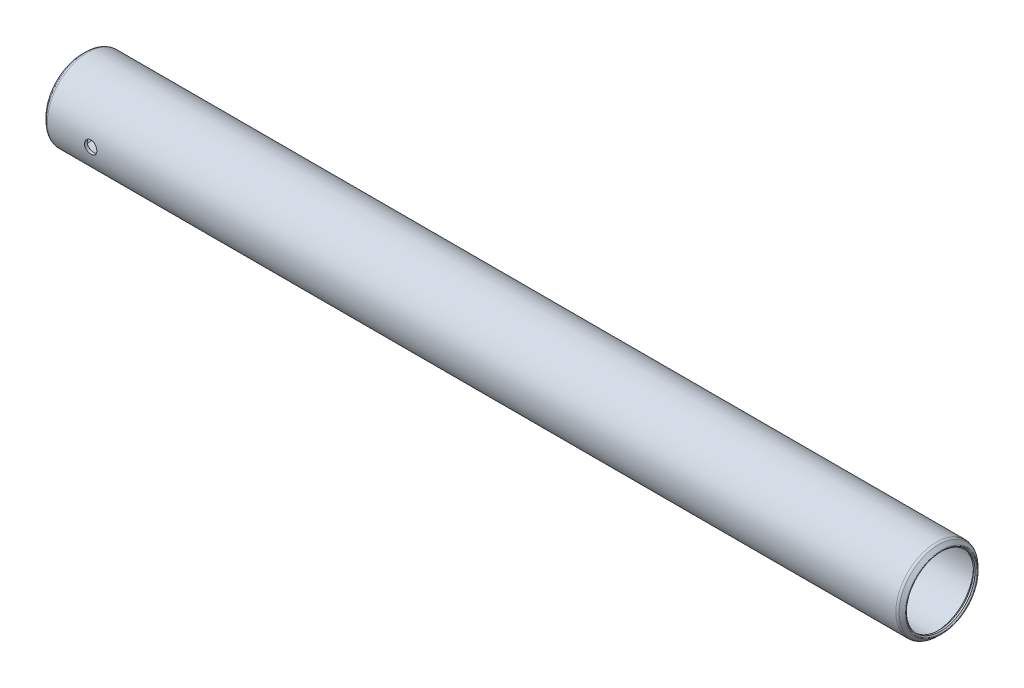
SolidWorks part; units mm, degrees
material "Cast Alloy Steel"
ref_plane "Front Plane" through (0, 0, 0) normal (0, 0, 1) x (1, 0, 0)
ref_plane "Top Plane" through (0, 0, 0) normal (0, 1, 0) x (1, 0, 0)
ref_plane "Right Plane" through (0, 0, 0) normal (1, 0, 0) x (0, 0, -1)
ref_plane "Plane1" through (164.8714, 0, 0) normal (1, 0, 0) x (0, 0, -1)
sketch "Sketch1" plane through (0, 0, 0) normal (0, 0, 1) x (1, 0, 0)
  line L0 (-0.518, 6.8362) -> (-0.3175, 6.6357)
  line L1 (-0.3175, 6.6357) -> (0, 6.6357)
  line L2 (0, 6.6357) -> (0.635, 7.2707)
  line L3 (0.635, 7.2707) -> (164.2364, 7.2707)
  line L4 (164.2364, 7.2707) -> (164.8714, 6.6357)
  line L5 (164.8714, 6.6357) -> (165.1889, 6.6357)
  line L6 (165.1889, 6.6357) -> (165.3894, 6.8362)
  line L7 (165.3894, 7.0158) -> (164.7807, 7.6245)
  line L8 (164.3316, 7.8105) -> (0.5398, 7.8105)
  line L9 (0.0907, 7.6245) -> (-0.518, 7.0158)
  line L10 (164.8714, 0) -> (0, 0) construction
  arc A0 (-0.518, 7.0158) -> (-0.518, 6.8362) centre (-0.4282, 6.926) ccw
  arc A1 (165.3894, 6.8362) -> (165.3894, 7.0158) centre (165.2996, 6.926) ccw
  arc A2 (164.7807, 7.6245) -> (164.3316, 7.8105) centre (164.3316, 7.1755) ccw
  arc A3 (0.5398, 7.8105) -> (0.0907, 7.6245) centre (0.5397, 7.1755) ccw
revolve "Revolve1" add sketch "Sketch1" angle 360 about L10 reverse direction yes
sketch "Sketch2" plane through (0, 0, 0) normal (0, 0, 1) x (1, 0, 0)
  circle A0 centre (8.89, 0) radius 1.1938
extrude "Cut-Extrude1" cut sketch "Sketch2" along normal blind 7.8105
ref_plane "Plane2" through (82.4357, 0, 0) normal (1, 0, 0) x (0, 0, -1)
ref_plane "cp1 XY" through (82.4357, 0, 0) normal (1, 0, 0) x (0, 0, -1)
ref_plane "cp1 XZ" through (0, 7.8105, 0) normal (0, -1, 0) x (-1, 0, 0)
ref_plane "cp1 YZ" through (0, 0, 0) normal (0, 0, -1) x (-1, 0, 0)
ref_axis "cp1 X" through (82.4357, 7.8105, 80.9) along (0, 0, -1)
ref_axis "cp1 Y" through (82.4357, -50, 0) along (0, 1, 0)
ref_axis "cp1 Z" through (80.9, 7.8105, 0) along (-1, 0, 0)
sketch3d "cp1"
  point P0 (82.4357, 7.8105, 0)
ref_plane "cp2 XY" through (82.4357, 0, 0) normal (1, 0, 0) x (0, 0, -1)
ref_plane "cp2 XZ" through (0, 0, 0) normal (0, -1, 0) x (-1, 0, 0)
ref_plane "cp2 YZ" through (0, 0, -7.8105) normal (0, 0, -1) x (-1, 0, 0)
ref_axis "cp2 X" through (82.4357, 0, 80.9) along (0, 0, -1)
ref_axis "cp2 Y" through (82.4357, -50, -7.8105) along (0, 1, 0)
ref_axis "cp2 Z" through (80.9, 0, -7.8105) along (-1, 0, 0)
sketch3d "cp2"
  point P0 (82.4357, 0, -7.8105)
ref_plane "cp3 XY" through (82.4357, 0, 0) normal (1, 0, 0) x (0, 0, -1)
ref_plane "cp3 XZ" through (0, -7.8105, 0) normal (0, -1, 0) x (-1, 0, 0)
ref_plane "cp3 YZ" through (0, 0, 0) normal (0, 0, -1) x (-1, 0, 0)
ref_axis "cp3 X" through (82.4357, -7.8105, 80.9) along (0, 0, -1)
ref_axis "cp3 Y" through (82.4357, -50, 0) along (0, 1, 0)
ref_axis "cp3 Z" through (80.9, -7.8105, 0) along (-1, 0, 0)
sketch3d "cp3"
  point P0 (82.4357, -7.8105, 0)
ref_plane "cp4 XY" through (82.4357, 0, 0) normal (1, 0, 0) x (0, 0, -1)
ref_plane "cp4 XZ" through (0, 0, 0) normal (0, -1, 0) x (-1, 0, 0)
ref_plane "cp4 YZ" through (0, 0, 7.8105) normal (0, 0, -1) x (-1, 0, 0)
ref_axis "cp4 X" through (82.4357, 0, 80.9) along (0, 0, -1)
ref_axis "cp4 Y" through (82.4357, -50, 7.8105) along (0, 1, 0)
ref_axis "cp4 Z" through (80.9, 0, 7.8105) along (-1, 0, 0)
sketch3d "cp4"
  point P0 (82.4357, 0, 7.8105)
ref_plane "tube_front XY" through (0, 0, 0) normal (1, 0, 0) x (0, 0, -1)
ref_plane "tube_front XZ" through (0, 0, 0) normal (0, -1, 0) x (-1, 0, 0)
ref_plane "tube_front YZ" through (0, 0, 0) normal (0, 0, -1) x (-1, 0, 0)
ref_axis "tube_front X" through (0, 0, 80.9) along (0, 0, -1)
ref_axis "tube_front Y" through (0, -50, 0) along (0, 1, 0)
ref_axis "tube_front Z" through (80.9, 0, 0) along (-1, 0, 0)
sketch3d "tube_front"
  point P0 (0, 0, 0)
ref_plane "tube_rear XY" through (164.8714, 0, 0) normal (1, 0, 0) x (0, 0, -1)
ref_plane "tube_rear XZ" through (0, 0, 0) normal (0, -1, 0) x (-1, 0, 0)
ref_plane "tube_rear YZ" through (0, 0, 0) normal (0, 0, -1) x (-1, 0, 0)
ref_axis "tube_rear X" through (164.8714, 0, 80.9) along (0, 0, -1)
ref_axis "tube_rear Y" through (164.8714, -50, 0) along (0, 1, 0)
ref_axis "tube_rear Z" through (80.9, 0, 0) along (-1, 0, 0)
sketch3d "tube_rear"
  point P0 (164.8714, 0, 0)
